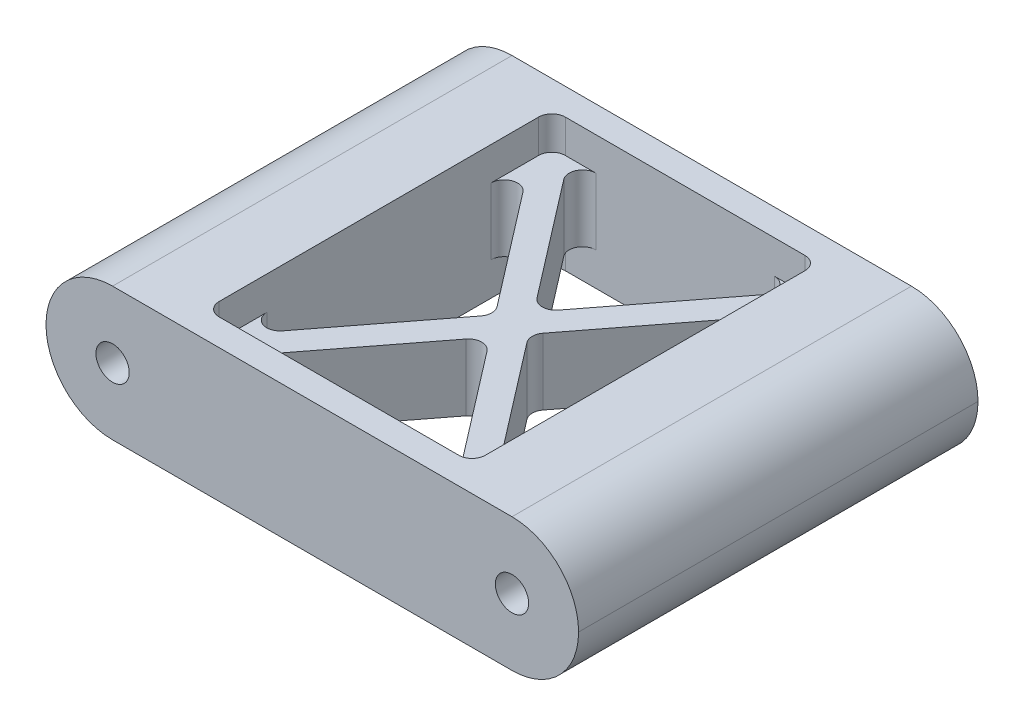
SolidWorks part; units mm, degrees
ref_plane "Спереди" through (0, 0, 0) normal (0, 0, 1) x (1, 0, 0)
ref_plane "Сверху" through (0, 0, 0) normal (0, 1, 0) x (1, 0, 0)
ref_plane "Справа" through (0, 0, 0) normal (1, 0, 0) x (0, 0, -1)
sketch "Эскиз1" plane through (0, 0, 0) normal (0, 1, 0) x (1, 0, 0)
  line L0 (0, 15) -> (0, -15) construction
  line L1 (-20, 15) -> (20, 15)
  line L2 (-20, 15) -> (-20, -15)
  line L3 (-20, -15) -> (20, -15)
  line L4 (20, 15) -> (20, -15)
  line L6 (-20, 0) -> (20, 0) construction
  point P8 (0, 0)
  dimension "D1" = 30
  dimension "D2" = 40
extrude "тело" add sketch "Эскиз1" along normal blind 5 and the other way blind 5
sketch "Эскиз5" plane through (0, 0, 15) normal (0, 0, 1) x (1, 0, 0)
  line L0 (-20, 0) -> (20, 0) construction
  line L1 (-20, -5) -> (-20, 5) construction
  line L2 (20, -5) -> (20, 5) construction
  line L4 (-20, 5) -> (20, 5) construction
  line L5 (0, 5) -> (0, -5) construction
  line L6 (-20, -5) -> (20, -5) construction
  circle A0 centre (-15, 0) radius 1.25
  circle A1 centre (15, 0) radius 1.25
  dimension "D1" = 2.5
  dimension "D2" = 5
  dimension "D3" = 30
extrude "отверстие под шурупы" cut sketch "Эскиз5" against normal through all
sketch "Эскиз6" plane through (0, 5, 0) normal (0, 1, 0) x (1, 0, 0)
  line L0 (-10, 13) -> (10, -13) construction
  line L1 (-10, 13) -> (10, 13) construction
  line L2 (-10, 13) -> (-10, -13) construction
  line L3 (-10, -13) -> (10, -13) construction
  line L4 (10, 13) -> (10, -13) construction
  line L5 (10, 13) -> (-10, -13) construction
  line L6 (-8.7384, 13) -> (8.7384, 13)
  line L7 (10, 11.3599) -> (10, -11.3599)
  line L8 (-8.7384, -13) -> (8.7384, -13)
  line L9 (-8.7384, 13) -> (0, 1.6401)
  line L11 (-10, 11.3599) -> (-10, -11.3599)
  line L12 (8.7384, 13) -> (0, 1.6401)
  line L13 (-10, 11.3599) -> (-1.2616, 0)
  line L14 (-8.7384, -13) -> (0, -1.6401)
  line L15 (-1.2616, 0) -> (-10, -11.3599)
  line L16 (1.2616, 0) -> (10, 11.3599)
  line L17 (1.2616, 0) -> (10, -11.3599)
  line L18 (0, -1.6401) -> (8.7384, -13)
  line L19 (0, 1.6401) -> (1.2616, 0) construction
  line L20 (-1.2616, 0) -> (0, 1.6401) construction
  line L21 (-1.2616, 0) -> (0, -1.6401) construction
  line L22 (1.2616, 0) -> (0, -1.6401) construction
  line L23 (20, 15) -> (-20, 15) construction
  line L24 (20, -15) -> (20, 15) construction
  point P4 (0, 0)
  point P13 (-10, 0)
  point P14 (-10, 0)
  point P16 (10, 0)
  point P18 (10, 0)
  point P19 (0, 13)
  point P20 (0, 13)
  point P21 (0, -13)
  point P22 (0, -13)
  point P23 (-0.6308, 0.8201)
  dimension "D1" = 2
  dimension "D2" = 2
  dimension "D3" = 10
extrude "ребра" cut sketch "Эскиз6" against normal through all
sketch "Эскиз7" plane through (0, 5, 0) normal (0, 1, 0) x (1, 0, 0)
  line L1 (-10, 13) -> (10, 13)
  line L2 (-10, 13) -> (-10, -13)
  line L3 (-10, -13) -> (10, -13)
  line L4 (10, 13) -> (10, -13)
extrude "углубления ребер" cut sketch "Эскиз7" against normal blind 2.5
mirror "Зеркальное отражение1" about plane through (0, 0, 0) normal (0, 1, 0) of "углубления ребер"
fillet "Скругление1" radius 1 16 edges at (-10, -3.75, -13) (-10, 3.75, -13) (-8.7384, 0, -13) (-10, 0, -11.3599) (10, -3.75, 13) (8.7384, 0, 13) (10, 0, 11.3599) (10, 3.75, 13) (-10, -3.75, 13) (-8.7384, 0, 13) (-10, 0, 11.3599) (-10, 3.75, 13) (10, -3.75, -13) (10, 0, -11.3599) (8.7384, 0, -13) (10, 3.75, -13)
fillet "Скругление2" radius 1 4 edges at (-1.2616, 0, 0) (0, 0, -1.6401) (1.2616, 0, 0) (0, 0, 1.6401)
fillet "Скругление3" radius 5 4 edges at (-20, -5, 0) (-20, 5, 0) (20, -5, 0) (20, 5, 0)
